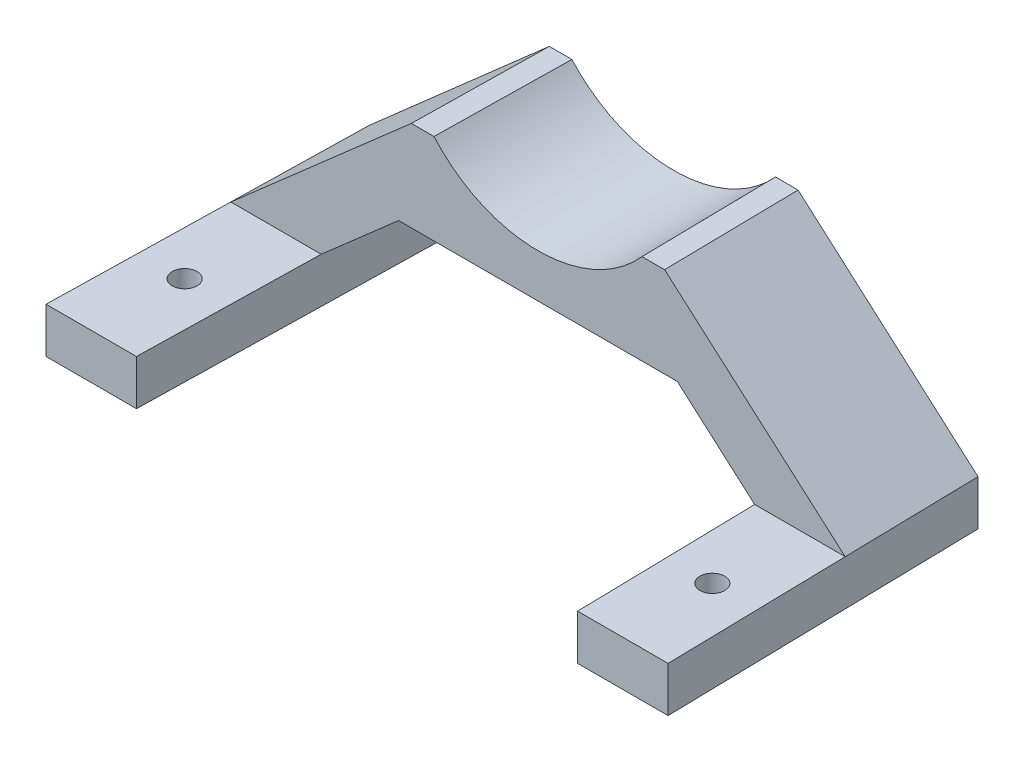
SolidWorks part; units mm, degrees
ref_plane "Front Plane" through (0, 0, 0) normal (0, 0, 1) x (1, 0, 0)
ref_plane "Top Plane" through (0, 0, 0) normal (0, 1, 0) x (1, 0, 0)
ref_plane "Right Plane" through (0, 0, 0) normal (1, 0, 0) x (0, 0, -1)
sketch "Sketch1" plane through (0, 0, 0) normal (0, 1, 0) x (1, 0, 0)
  line L0 (0, 0) -> (20.0045, 0)
  line L1 (20.0045, 0) -> (21.4891, 70)
  line L2 (21.4891, 70) -> (1.4846, 70)
  line L3 (1.4846, 70) -> (0, 0)
  line L4 (68.7637, 0) -> (68.7637, 140) construction
  line L5 (21.4891, 70) -> (22.9737, 140) construction
  line L6 (116.0384, 70) -> (136.0429, 70)
  line L7 (117.523, 0) -> (116.0384, 70)
  line L8 (137.5275, 0) -> (117.523, 0)
  line L9 (136.0429, 70) -> (137.5275, 0)
  line L10 (0.4332, 20.4241) -> (20.4287, 20) construction
  circle A0 centre (10.4309, 20.212) radius 2.75
  circle A2 centre (127.0966, 20.212) radius 2.75
  dimension "D6" = 5.5
  dimension "D1" = 1.215
  dimension "D2" = 45.79
  dimension "D3" = 20
  dimension "D4" = 70
  dimension "D5" = 140
  dimension "D7" = 20
extrude "Boss-Extrude1" add sketch "Sketch1" along normal blind 10
sketch "Sketch2" plane through (0, 0, -70) normal (0, 0, -1) x (-1, 0, 0)
  line L0 (-21.4891, 10) -> (-1.4846, 10) construction
  line L1 (-116.0384, 10) -> (-21.4891, 10) construction
  line L2 (-68.7637, 10) -> (-68.7637, 35) construction
  line L3 (-91.2637, 45) -> (-96.2637, 45)
  line L4 (-46.2637, 45) -> (-41.2637, 45)
  line L5 (-98.9902, 25) -> (-38.5373, 25)
  line L6 (-38.5373, 25) -> (-21.4891, 10)
  line L7 (-98.9902, 25) -> (-116.0384, 10)
  line L8 (-116.0384, 10) -> (-136.0429, 10)
  line L9 (-136.0429, 10) -> (-96.2637, 45)
  line L10 (-41.2637, 45) -> (-1.4846, 10)
  line L11 (-1.4846, 10) -> (-21.4891, 10)
  arc A0 (-91.2637, 45) -> (-46.2637, 45) centre (-68.7637, 65.3125) ccw
  point P3 (-68.7637, 35)
  point P16 (-68.7637, 54.3719)
  dimension "D5" = 45
  dimension "D1" = 25
  dimension "D2" = 5
  dimension "D3" = 10
  dimension "D4" = 10
ref_plane "Plane1" through (0, 0, -40) normal (0, 0, -1) x (-1, 0, 0)
sketch "Sketch3" plane through (0, 0, -40) normal (0, 0, -1) x (-1, 0, 0)
  line L0 (-136.6791, 10) -> (-96.7637, 45)
  line L1 (-96.7637, 45) -> (-91.7637, 45)
  line L2 (-99.568, 25) -> (-37.9595, 25)
  line L3 (-68.7637, 10) -> (-68.7637, 35) construction
  line L4 (-68.7637, 10) -> (-68.7637, 35) construction
  line L5 (-45.7637, 45) -> (-40.7637, 45)
  line L6 (-40.7637, 45) -> (-0.8484, 10)
  line L7 (-0.8484, 10) -> (-20.8529, 10)
  line L8 (-20.8529, 10) -> (-37.9595, 25)
  line L9 (-99.568, 25) -> (-116.6746, 10)
  line L10 (-116.6746, 10) -> (-136.6791, 10)
  line L11 (-98.9902, 25) -> (-38.5373, 25) construction
  line L19 (-91.2637, 45) -> (-96.2637, 45) construction
  arc A0 (-91.7637, 45) -> (-45.7637, 45) centre (-68.7637, 65.3125) ccw
  point P26 (-68.7637, 34.627)
  dimension "D1" = 5
  dimension "D2" = 46
loft "Loft1" add profiles "Sketch2", "Sketch3" connector at (46.2637, 45, -70) connector at (45.7637, 45, -40)
